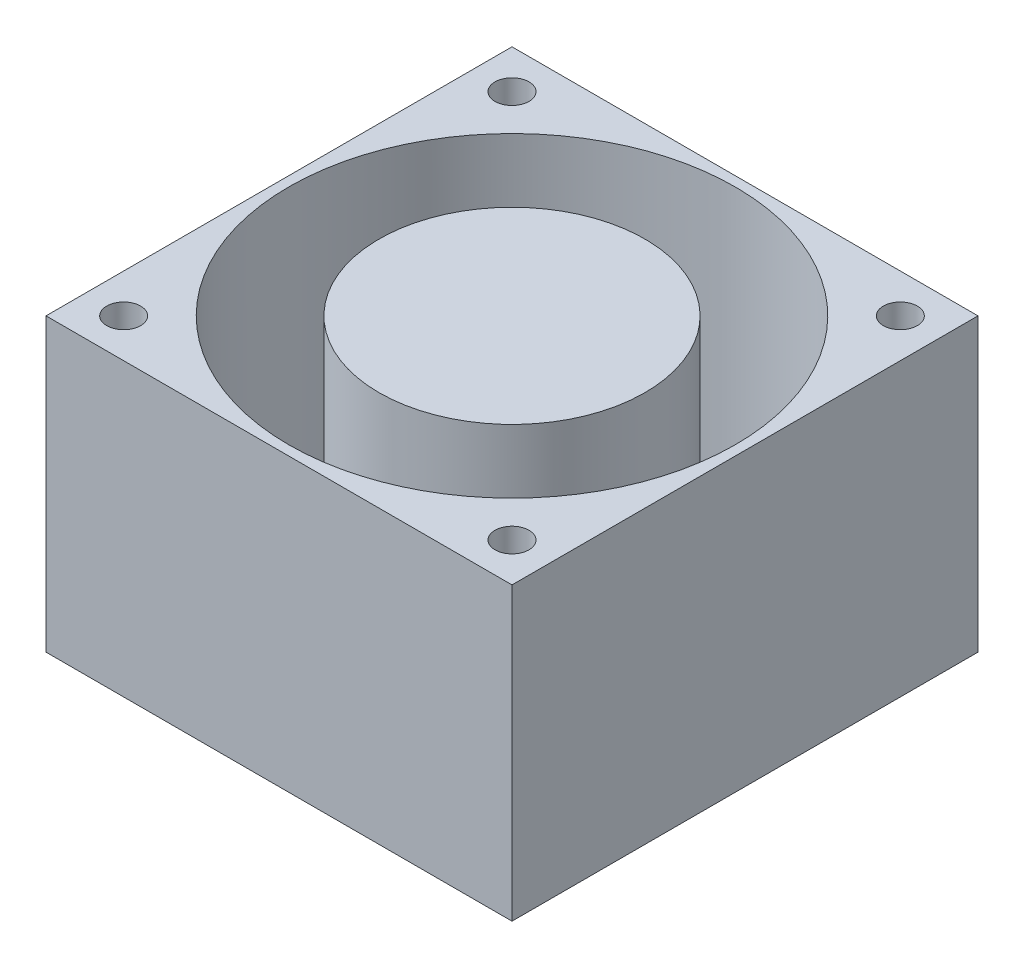
SolidWorks part; units mm, degrees
ref_plane "Front" through (0, 0, 0) normal (0, 0, 1) x (1, 0, 0)
ref_plane "Top" through (0, 0, 0) normal (0, 1, 0) x (1, 0, 0)
ref_plane "Right" through (0, 0, 0) normal (1, 0, 0) x (0, 0, -1)
sketch "Sketch1" plane through (0, 0, 0) normal (0, 1, 0) x (1, 0, 0)
  line L0 (0, 0) -> (0, -30.48)
  line L1 (0, -30.48) -> (30.48, -30.48)
  line L2 (30.48, -30.48) -> (30.48, 30.48)
  line L3 (30.48, 30.48) -> (-30.48, 30.48)
  line L4 (-30.48, 30.48) -> (-30.48, -30.48)
  line L5 (-30.48, -30.48) -> (0, -30.48)
  line L6 (0, 30.48) -> (0, 25.4)
  line L7 (0, 25.4) -> (25.4, 25.4) construction
  line L8 (25.4, 25.4) -> (25.4, -25.4) construction
  line L9 (25.4, -25.4) -> (-25.4, -25.4) construction
  line L10 (-25.4, -25.4) -> (-25.4, 25.4) construction
  line L11 (-25.4, 25.4) -> (0, 25.4) construction
  circle A0 centre (0, 0) radius 17.399
  circle A1 centre (0, 0) radius 29.21
  circle A2 centre (-25.4, 25.4) radius 2.2225
  circle A3 centre (-25.4, -25.4) radius 2.2225
  circle A4 centre (25.4, -25.4) radius 2.2225
  circle A5 centre (25.4, 25.4) radius 2.2225
extrude "Boss-Extrude1" add sketch "Sketch1" along normal blind 38.1 contours A0 | A1 L6 L3 L4 L5 L0 A3 A2 | A1 L0 L1 L2 L3 L6 A5 A4 region at (21.1365, 0, 21.1365) region at (-0.6816, 0, 29.845) region at (-11.955, 0, -11.955)
sketch "Sketch2" plane through (0, 0, 0) normal (0, -1, 0) x (1, 0, 0)
  line L0 (0, 0) -> (-30.48, 0) construction
  line L1 (-30.48, -30.48) -> (-30.48, 30.48) construction
  line L2 (0, 1.27) -> (-30.48, 1.27)
  line L3 (0, -1.27) -> (-30.48, -1.27)
  line L4 (0, 1.27) -> (0, -1.27)
  line L5 (-30.48, 1.27) -> (-30.48, -1.27)
  line L6 (-1.2078, -0.3925) -> (-10.6267, 28.5958)
  line L7 (1.2078, 0.3925) -> (-8.211, 29.3807)
  line L8 (-8.211, 29.3807) -> (-10.6267, 28.5958)
  line L9 (-0.7465, 1.0275) -> (23.9124, 18.9431)
  line L10 (0.7465, -1.0275) -> (25.4053, 16.8882)
  line L11 (25.4053, 16.8882) -> (23.9124, 18.9431)
  line L12 (0.7465, 1.0275) -> (25.4053, -16.8882)
  line L13 (-0.7465, -1.0275) -> (23.9124, -18.9431)
  line L14 (23.9124, -18.9431) -> (25.4053, -16.8882)
  line L15 (1.2078, -0.3925) -> (-8.211, -29.3807)
  line L16 (-1.2078, 0.3925) -> (-10.6267, -28.5958)
  line L17 (-10.6267, -28.5958) -> (-8.211, -29.3807)
  point P27 (0, 0)
  circle M6 centre (0, 0) radius 17.399
  dimension "D1" = 1.27
  dimension "D2" = 1.27
  dimension "D3" = 5
extrude "Boss-Extrude2" add sketch "Sketch2" against normal blind 2.54 contours L7 L8 L6 M6 | L10 L11 L9 M6 | L13 L14 L12 M6 | L16 L17 L15 M6 | L0 L5 L3 M6 | L0 L2 L5 M6 region at (-23.9318, 0, -0.6354) region at (-23.9318, 0, 0.6354) region at (-7.3953, 0, 22.7605) region at (-7.3953, 0, -22.7605) region at (19.3612, 0, 14.0667) region at (19.3612, 0, -14.0667)
